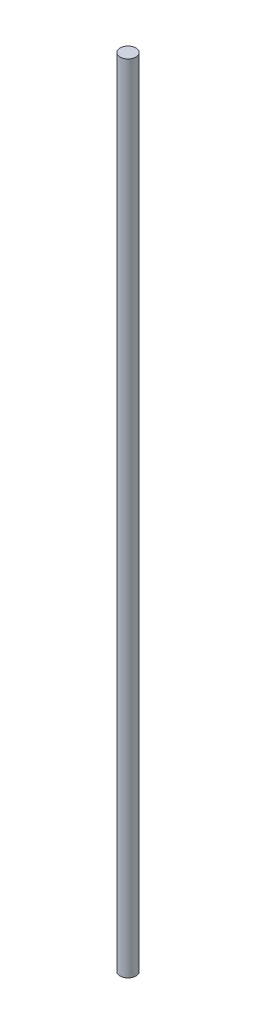
SolidWorks part; units mm, degrees
material "AISI 1020"
ref_plane "Front Plane" through (0, 0, 0) normal (0, 0, 1) x (1, 0, 0)
ref_plane "Top Plane" through (0, 0, 0) normal (0, 1, 0) x (1, 0, 0)
ref_plane "Right Plane" through (0, 0, 0) normal (1, 0, 0) x (0, 0, -1)
sketch "Sketch1" plane through (0, 0, 0) normal (0, 1, 0) x (1, 0, 0)
  circle A0 centre (0, 0) radius 4
  dimension "D1" = 8
extrude "Boss-Extrude1" add sketch "Sketch1" along normal blind 200 and the other way blind 200
cosmetic thread "Cosmetic Thread1" parameters "D2"=7
